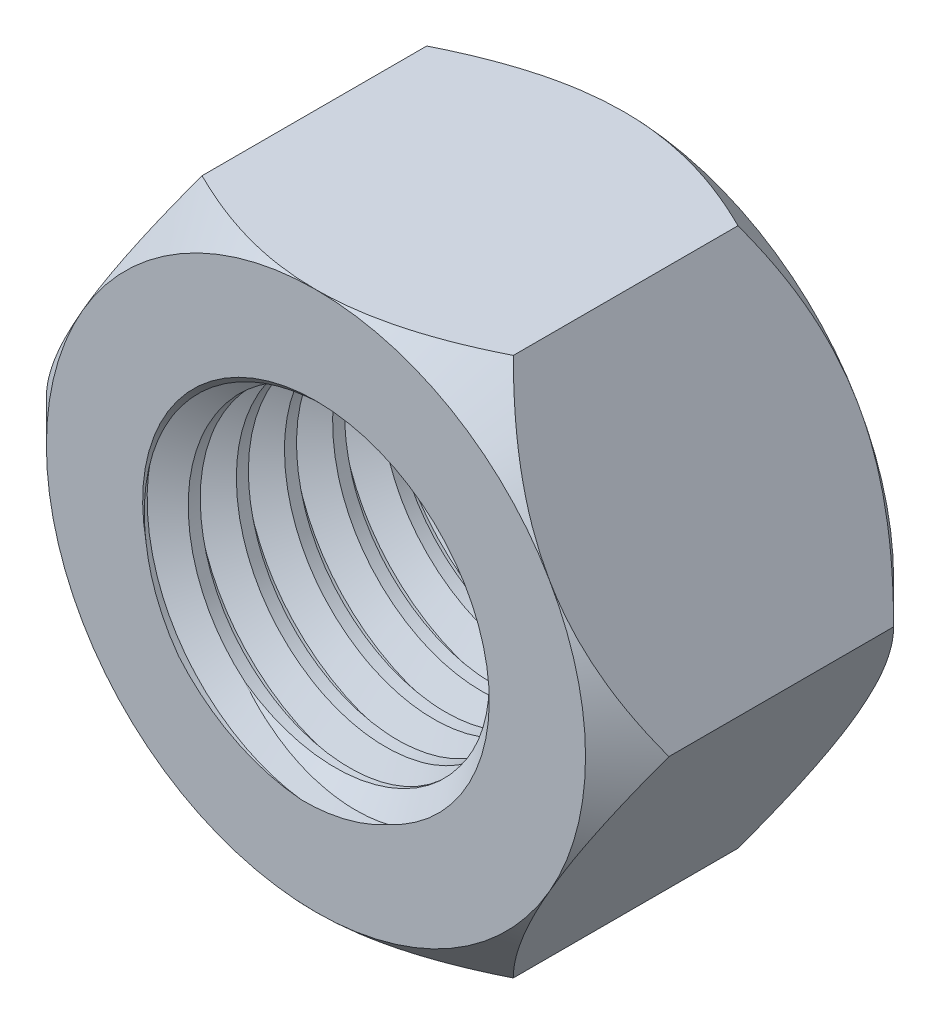
SolidWorks part; units mm, degrees
ref_plane "Front Plane" through (0, 0, 0) normal (0, 0, 1) x (1, 0, 0)
ref_plane "Top Plane" through (0, 0, 0) normal (0, 1, 0) x (1, 0, 0)
ref_plane "Right Plane" through (0, 0, 0) normal (1, 0, 0) x (0, 0, -1)
sketch "Sketch1" plane through (0, 0, 0) normal (0, 0, 1) x (1, 0, 0)
  line L1 (4.0415, -7) -> (8.0829, 0)
  line L2 (8.0829, 0) -> (4.0415, 7)
  line L3 (4.0415, 7) -> (-4.0415, 7)
  line L4 (-4.0415, 7) -> (-8.0829, 0)
  line L5 (-8.0829, 0) -> (-4.0415, -7)
  line L6 (-4.0415, -7) -> (4.0415, -7)
  circle A0 centre (0, 0) radius 7 construction
  dimension "D1" = 14
extrude "Boss-Extrude1" add sketch "Sketch1" along normal mid plane 8
sketch "Sketch2" plane through (0, 0, 4) normal (0, 0, 1) x (1, 0, 0)
  circle A0 centre (0, 0) radius 7
extrude "Cut-Extrude1" cut sketch "Sketch2" against normal through all draft 45 flip side to cut
mirror "Mirror1" about plane through (0, 0, 0) normal (0, 0, 1) of "Cut-Extrude1"
sketch "Sketch3" plane through (0, 0, 4) normal (0, 0, 1) x (1, 0, 0)
  circle A0 centre (0, 0) radius 4
extrude "Cut-Extrude2" cut sketch "Sketch3" against normal through all
chamfer "Chamfer1" distance 0.5 angle 45 2 edges at (4, 0, -4) (4, 0, 4)
thread "Thread1" pitch 1.25 method cut profile "Thread Profile1" start angle 0, offset 2, length 0, pitch 1.25, diameter 8
ref_plane "Plane1" through (-4, 0, 5.5) normal (0, -1, 0) x (-1, 0, 0)
sketch "Thread Profile1" plane through (-4, 0, 5.5) normal (0, -1, 0) x (-1, 0, 0)
  line L0 (0, 0) -> (0, 1.25) construction
  line L1 (0, 0) -> (0.6766, 0.3906)
  line L2 (0.6766, 0.3906) -> (0.6766, 0.5469)
  line L3 (0.6766, 0.5469) -> (0, 0.9375)
  line L4 (0.6766, 0.4687) -> (0, 0.4687) construction
  line L11 (0, 0) -> (0, 0.9375)
  point P2 (0, 0)
  dimension "Pitch" = 1.25
  dimension "Profile_Angle" = 60
  dimension "Profile_Land" = 0.1562
  dimension "Profile_Height" = 0.6766
